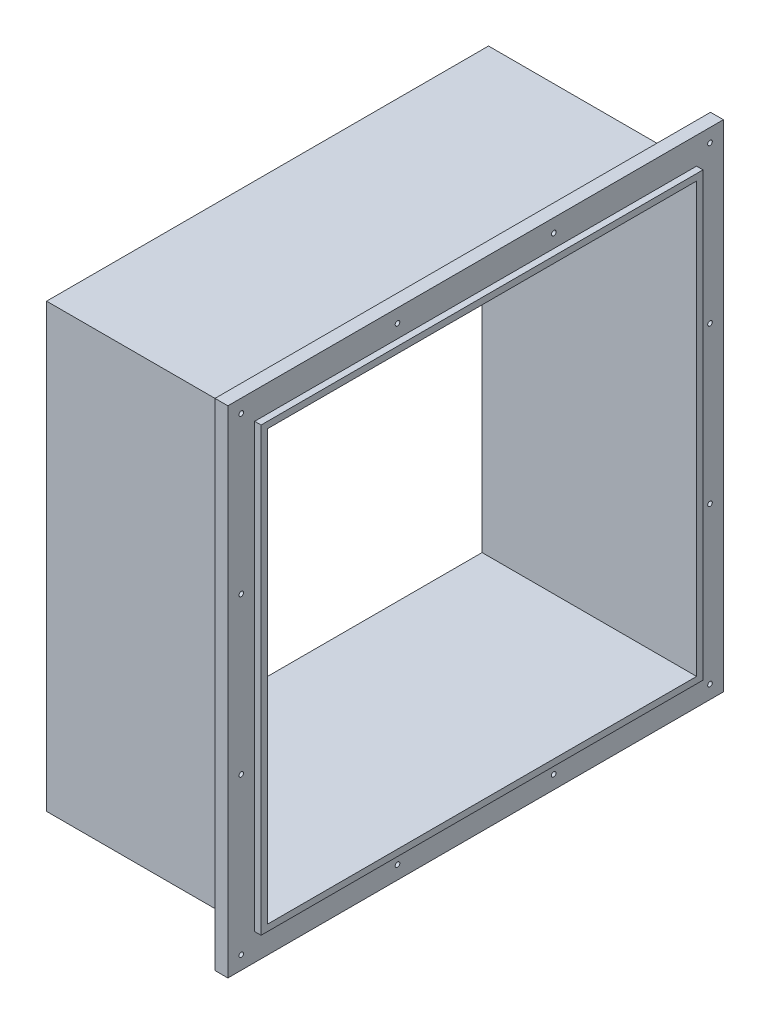
SolidWorks part; units mm, degrees
other "Markup1"
sketch "Sketch4" plane through (205, 243, -243) normal (0.9832, 0.1824, -0.0072) x (-0.0237, 0.0882, -0.9958)
material "Teak"
ref_plane "Front Plane" through (0, 0, 0) normal (0, 0, 1) x (1, 0, 0)
ref_plane "Top Plane" through (0, 0, 0) normal (0, 1, 0) x (1, 0, 0)
ref_plane "Right Plane" through (0, 0, 0) normal (1, 0, 0) x (0, 0, -1)
sketch "Sketch1" plane through (0, 0, 0) normal (1, 0, 0) x (0, 0, -1)
  line L1 (200, -200) -> (-200, -200)
  line L2 (200, -200) -> (200, 200)
  line L3 (200, 200) -> (-200, 200)
  line L4 (-200, -200) -> (-200, 200)
  line L5 (200, -200) -> (-200, 200) construction
  line L6 (200, 200) -> (-200, -200) construction
  point P0 (0, 0)
  dimension "D1" = 400
extrude "Extrude-Thin1" add sketch "Sketch1" along normal blind 200 thin thin type one direction wall 6
ref_plane "Plane1" through (194, 0, 0) normal (1, 0, 0) x (0, 0, -1)
sketch "Sketch5" plane through (194, 0, 0) normal (1, 0, 0) x (0, 0, -1)
  line L1 (206, -206) -> (-206, -206)
  line L2 (206, -206) -> (206, 206)
  line L3 (206, 206) -> (-206, 206)
  line L4 (-206, -206) -> (-206, 206)
  line L5 (206, -206) -> (-206, 206) construction
  line L6 (206, 206) -> (-206, -206) construction
  point P0 (0, 0)
extrude "Extrude-Thin2" add sketch "Sketch5" against normal blind 12 thin thin type one direction wall 25
sketch "Sketch6" plane through (194, 0, 0) normal (1, 0, 0) x (0, 0, -1)
  line L0 (206, 206) -> (231, 231) construction
  line L1 (-231, 231) -> (-206, 206) construction
  line L2 (-218.5, 218.5) -> (218.5, 218.5) construction
  line L4 (0, 0) -> (0, 349.226) construction
  line L5 (0, 0) -> (-338.552, 0) construction
  circle A0 centre (-218.5, 218.5) radius 2.15
  circle A1 centre (-72.83, 218.5) radius 2.15
  circle A2 centre (72.84, 218.5) radius 2.15
  circle A3 centre (-218.5, 72.83) radius 2.15
  circle A4 centre (-218.5, -72.84) radius 2.15
  circle A5 centre (218.5, 218.5) radius 2.15
  circle A6 centre (218.5, -218.5) radius 2.15
  circle A7 centre (72.84, -218.5) radius 2.15
  circle A8 centre (-72.83, -218.5) radius 2.15
  circle A9 centre (-218.5, -218.5) radius 2.15
  circle A10 centre (218.5, 72.83) radius 2.15
  circle A11 centre (218.5, -72.84) radius 2.15
  dimension "D1" = 4.3
  dimension "D5" = 145.67
  dimension "D2" = 145.67
  dimension "D3" = 145.67
  dimension "D4" = 3
extrude "Cut-Extrude1" cut sketch "Sketch6" against normal through all contours L1 A0 | L1 A0 | A1 | A2 | A4 | A8 | A7 | A11 | A3 | A9 | A6 | A10 | A5 region at (194, 218.5, 218.5) region at (194, 218.5, 72.83) region at (194, 218.5, -72.84) region at (194, -72.84, 218.5) region at (194, -218.5, -72.84) region at (194, -218.5, 72.83) region at (194, -72.84, -218.5)
